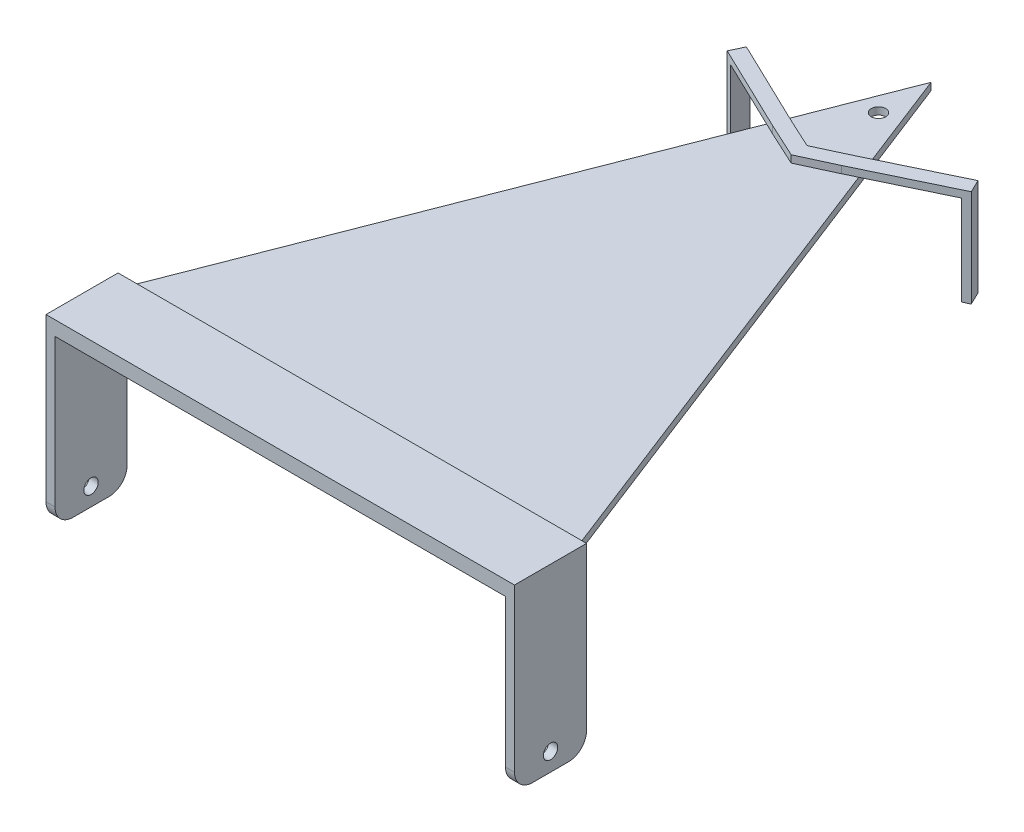
SolidWorks part; units mm, degrees
ref_plane "Front Plane" through (0, 0, 0) normal (0, 0, 1) x (1, 0, 0)
ref_plane "Top Plane" through (0, 0, 0) normal (0, 1, 0) x (1, 0, 0)
ref_plane "Right Plane" through (0, 0, 0) normal (1, 0, 0) x (0, 0, -1)
sketch "Sketch2" plane through (0, 0, 0) normal (0, 1, 0) x (1, 0, 0)
  line L3 (62.5, 179.2193) -> (62.5, 26.7241) construction
  line L4 (125, 0) -> (125, 10)
  line L5 (125, 10) -> (62.5, 170.6168)
  line L6 (125, 0) -> (125, -10)
  line L7 (125, -10) -> (0, -10)
  line L8 (0, -10) -> (0, 0)
  line L9 (0, 10) -> (62.5, 170.6168)
  line L10 (0, 0) -> (0, 10)
  line L11 (0, 0) -> (125, 0) construction
  circle A0 centre (62.5, 156.0248) radius 2
  point P3 (62.5, 156.0248)
  point P13 (130, 0)
  point P16 (-5, 0)
  dimension "D5" = 10
  dimension "D1" = 125
  dimension "D2" = 170
  dimension "D3" = 5
  dimension "D4" = 62.5
  dimension "D6" = 10
  dimension "D7" = 10
  dimension "D8" = 10
  dimension "D9" = 5
  dimension "D10" = 170
extrude "Boss-Extrude1" add sketch "Sketch2" along normal blind 2
sketch "Sketch4" plane through (0, 2, 0) normal (0, 1, 0) x (1, 0, 0)
  line L1 (0, 10) -> (125, 10)
  line L2 (0, 10) -> (0, -10)
  line L3 (0, -10) -> (125, -10)
  line L4 (125, 10) -> (125, -10)
  line L5 (125, 10) -> (127, 10)
  line L6 (125, 10) -> (125, -10)
  line L7 (125, -10) -> (127, -10)
  line L8 (127, 10) -> (127, -10)
  line L9 (0, 10) -> (-2, 10)
  line L10 (0, 10) -> (0, -10)
  line L11 (0, -10) -> (-2, -10)
  line L12 (-2, 10) -> (-2, -10)
  line M3 (0, 10) -> (0, -10)
  line M4 (0, -10) -> (125, -10)
  line M5 (125, -10) -> (125, 10)
  dimension "D1" = 2
  dimension "D2" = 2
extrude "Boss-Extrude4" add sketch "Sketch4" along normal blind 2 contours L1 M3 M4 M5 region at (62.5, 2, 0)
sketch "Sketch7" plane through (0, 4, 0) normal (0, 1, 0) x (1, 0, 0)
  line L1 (0, 10) -> (-2.5, 10)
  line L2 (0, 10) -> (0, -10)
  line L3 (0, -10) -> (-2.5, -10)
  line L4 (-2.5, 10) -> (-2.5, -10)
  line L5 (125, 10) -> (127.5, 10)
  line L6 (125, 10) -> (125, -10)
  line L7 (125, -10) -> (127.5, -10)
  line L8 (127.5, 10) -> (127.5, -10)
  dimension "D1" = 2.5
  dimension "D2" = 2.5
  dimension "D3" = 20
  dimension "D4" = 20
extrude "Boss-Extrude5" add sketch "Sketch7" against normal blind 50
fillet "Fillet1" radius 5 4 edges at (126.25, -46, 10) (126.25, -46, -10) (-1.25, -46, -10) (-1.25, -46, 10)
sketch "Sketch9" plane through (-2.5, 0, 0) normal (-1, 0, 0) x (0, 0, 1)
  line L0 (10, -41) -> (10, 4) construction
  line L1 (-5, -46) -> (5, -46) construction
  circle A0 centre (0, -41) radius 2
  dimension "D1" = 4
  dimension "D2" = 10
  dimension "D3" = 5
extrude "Cut-Extrude1" cut sketch "Sketch9" against normal blind 250
sketch "Sketch10" plane through (0, 2, 0) normal (0, 1, 0) x (1, 0, 0)
  line L0 (62.5, 153.2142) -> (62.5, 143.0513) construction
  line L1 (62.5, 0) -> (48.6616, 0) construction
  line L7 (52.9688, 136.1967) -> (30.4368, 147.0277)
  line L8 (62.5, 156.0248) -> (137.5, 0) construction
  line L9 (62.5, 156.0248) -> (-12.5, 0) construction
  line L10 (53.8352, 137.9993) -> (5.7036, 161.1358) construction
  line L11 (30.4368, 147.0277) -> (32.1697, 150.6328)
  line L12 (32.1697, 150.6328) -> (54.7017, 139.8018)
  line L13 (54.7017, 139.8018) -> (62.5, 136.1967)
  line L15 (62.5, 131.7904) -> (52.9688, 136.1967)
  line L16 (94.5632, 147.0277) -> (92.8303, 150.6328)
  line L17 (72.0312, 136.1967) -> (94.5632, 147.0277)
  line L18 (62.5, 131.7904) -> (72.0312, 136.1967)
  line L19 (70.2983, 139.8018) -> (62.5, 136.1967)
  line L20 (92.8303, 150.6328) -> (70.2983, 139.8018)
  point P1 (62.5, 148.8302)
  point P12 (-12.5, 0)
  point P15 (137.5, 0)
  point P20 (53.8352, 137.9993)
  point P21 (31.3032, 148.8302)
  dimension "D1" = 20
  dimension "D2" = 2
  dimension "D3" = 75
  dimension "D4" = 75
  dimension "D5" = 25
  dimension "D6" = 2
extrude "Boss-Extrude6" add sketch "Sketch10" along normal blind 2
sketch "Sketch11" plane through (134.2239, 0, -64.5204) normal (0.9013, 0, -0.4332) x (-0.4332, 0, -0.9013)
  line L0 (95.5446, 4) -> (95.5446, 2) construction
  line L1 (91.5446, 4) -> (95.5446, 4)
  line L2 (91.5446, 4) -> (91.5446, -23)
  line L3 (91.5446, -23) -> (95.5446, -23)
  line L4 (95.5446, 4) -> (95.5446, -23)
  line L5 (91.5446, 2) -> (95.5446, 2) construction
  dimension "D1" = 25
extrude "Boss-Extrude7" add sketch "Sketch11" along normal blind 2
sketch "Sketch12" plane through (-32.6858, 0, -15.7118) normal (-0.9013, 0, -0.4332) x (-0.4332, 0, 0.9013)
  line L0 (-145.6994, 4) -> (-145.6994, 2) construction
  line L1 (-149.6994, 4) -> (-145.6994, 4)
  line L2 (-149.6994, 4) -> (-149.6994, -23)
  line L3 (-149.6994, -23) -> (-145.6994, -23)
  line L4 (-145.6994, 4) -> (-145.6994, -23)
  line L5 (-149.6994, 2) -> (-145.6994, 2) construction
  point P9 (-147.6994, 2)
  dimension "D1" = 25
extrude "Boss-Extrude8" add sketch "Sketch12" along normal blind 2
equation "\"R\"= 150"
equation "\"d\"= 20"
